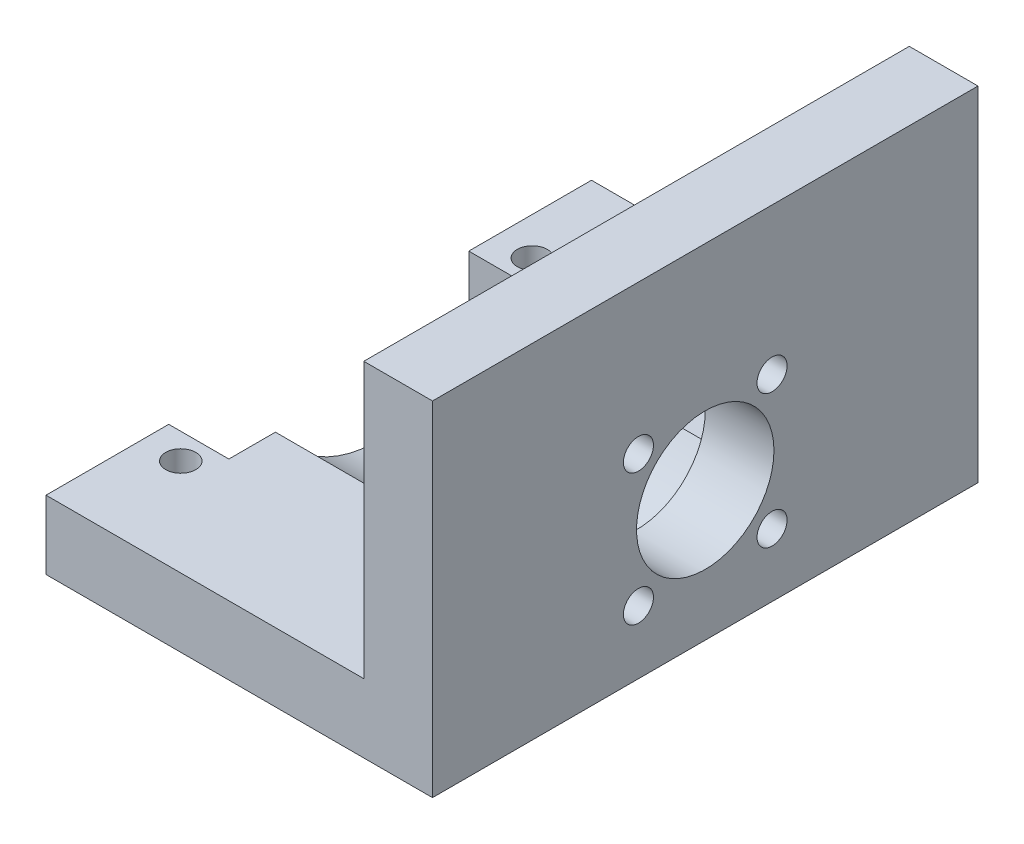
SolidWorks part; units mm, degrees
ref_plane "Front Plane" through (0, 0, 0) normal (0, 0, 1) x (1, 0, 0)
ref_plane "Top Plane" through (0, 0, 0) normal (0, 1, 0) x (1, 0, 0)
ref_plane "Right Plane" through (0, 0, 0) normal (1, 0, 0) x (0, 0, -1)
sketch "Sketch1" plane through (0, 0, 0) normal (0, 1, 0) x (1, 0, 0)
  line L0 (0, -17.465) -> (0, 17.465)
  line L1 (0, -55) -> (0, 55) construction
  line L2 (0, 17.465) -> (-7, 17.465)
  line L3 (-7, 17.465) -> (-7, 31.755)
  line L4 (-7, 31.755) -> (38, 31.755)
  line L5 (38, 31.755) -> (38, -31.755)
  line L6 (-55, 0) -> (55, 0) construction
  line L7 (38, 0) -> (0, 0)
  line L8 (-7, -31.755) -> (38, -31.755)
  line L9 (-7, -17.465) -> (-7, -31.755)
  line L10 (0, -17.465) -> (-7, -17.465)
  dimension "D1" = 7
  dimension "D2" = 31.755
  dimension "D3" = 17.465
  dimension "D4" = 45
extrude "Boss-Extrude1" add sketch "Sketch1" along normal blind 40 contours L0 L10 L9 L8 L5 L7 | L7 L5 L4 L3 L2 L0 region at (17.2776, 0, 16.546) region at (17.2776, 0, -16.546)
sketch "Sketch2" plane through (0, 0, 31.755) normal (0, 0, 1) x (1, 0, 0)
  line L0 (24.75, 0) -> (-24.75, 0) construction
  line L1 (-7, 40) -> (30, 40)
  line L2 (-7, 40) -> (-7, 8)
  line L3 (-7, 8) -> (30, 8)
  line L4 (30, 40) -> (30, 8)
  line L5 (38, 40) -> (38, 0) construction
  dimension "D1" = 8
  dimension "D2" = 8
extrude "Cut-Extrude1" cut sketch "Sketch2" against normal through all
sketch "Sketch4" plane through (38, 0, 0) normal (1, 0, 0) x (0, 0, -1)
  line L0 (0, 22) -> (0, -22) construction
  line L1 (24.75, 0) -> (-24.75, 0) construction
  line L3 (-7.7782, 7.3568) -> (7.7782, 7.3568) construction
  line L4 (-7.7782, 7.3568) -> (-7.7782, 22.9132) construction
  line L5 (-7.7782, 22.9132) -> (7.7782, 22.9132) construction
  line L6 (7.7782, 7.3568) -> (7.7782, 22.9132) construction
  line L7 (-7.7782, 7.3568) -> (7.7782, 22.9132) construction
  line L8 (-7.7782, 22.9132) -> (7.7782, 7.3568) construction
  circle A0 centre (0, 15.135) radius 8
  circle A1 centre (0, 15.135) radius 11 construction
  circle A2 centre (-7.7782, 22.6833) radius 1.75
  circle A3 centre (7.7782, 22.9132) radius 1.75
  circle A4 centre (7.7782, 7.3568) radius 1.75
  circle A5 centre (-7.7782, 7.3568) radius 1.75
  dimension "D1" = 16
  dimension "D2" = 15.135
  dimension "D3" = 22
  dimension "D4" = 3.5
extrude "Cut-Extrude2" cut sketch "Sketch4" against normal through all
sketch "Sketch5" plane through (0, 0, 0) normal (-1, 0, 0) x (0, 0, 1)
  circle A0 centre (0, 15.135) radius 14
  dimension "D1" = 28
extrude "Cut-Extrude3" cut sketch "Sketch5" against normal up to surface (30 mm away) up to face at (30, 24.6632, -7.7782)
sketch "Sketch6" plane through (0, 8, 0) normal (0, 1, 0) x (1, 0, 0)
  line L0 (-7, -17.465) -> (0, -17.465) construction
  line L1 (-7, -17.465) -> (-7, -31.755) construction
  circle A0 centre (-2.6, -20.465) radius 1.75
  dimension "D1" = 3.5
  dimension "D3" = 4.4
  dimension "D2" = 3
extrude "Cut-Extrude4" cut sketch "Sketch6" against normal through all
mirror "Mirror1" about plane through (0, 0, 0) normal (0, 0, 1) of "Cut-Extrude4"
